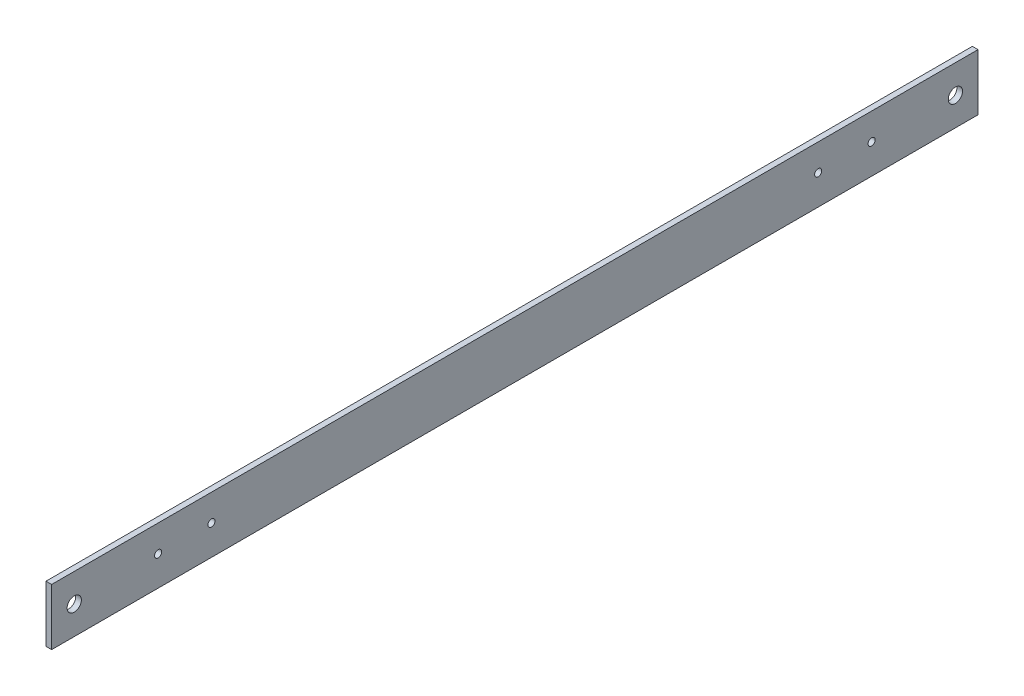
SolidWorks part; units mm, degrees
ref_plane "Front Plane" through (0, 0, 0) normal (0, 0, 1) x (1, 0, 0)
ref_plane "Top Plane" through (0, 0, 0) normal (0, 1, 0) x (1, 0, 0)
ref_plane "Right Plane" through (0, 0, 0) normal (1, 0, 0) x (0, 0, -1)
sketch "Sketch1" plane through (0, 0, 0) normal (1, 0, 0) x (0, 0, -1)
  line L1 (0, 0) -> (520.7, 0)
  line L2 (0, 0) -> (0, 31.75)
  line L3 (0, 31.75) -> (520.7, 31.75)
  line L4 (520.7, 0) -> (520.7, 31.75)
  circle A0 centre (12.7, 15.875) radius 4
  circle A1 centre (508, 15.875) radius 4
  circle A2 centre (59.825, 16.75) radius 2
  circle A3 centre (89.825, 16.75) radius 2
  circle A4 centre (430.875, 16.75) radius 2
  circle A5 centre (460.875, 16.75) radius 2
  dimension "D3" = 8
  dimension "D13" = 4
  dimension "D1" = 31.75
  dimension "D2" = 520.7
  dimension "D4" = 15.875
  dimension "D5" = 12.7
  dimension "D6" = 12.7
  dimension "D7" = 508
  dimension "D8" = 30
  dimension "D9" = 59.825
  dimension "D10" = 59.825
  dimension "D11" = 30
  dimension "D12" = 15
  dimension "D14" = 430.875
extrude "Boss-Extrude2" add sketch "Sketch1" along normal blind 3.175
equation "\"RailThickness\"= .125in'Spec"
equation "\"VSWidth\"= 1.25in'Spec"
equation "\"StepperHolePadSize\"= \"StepperHoleDiameter\""
equation "\"D1@Sketch1\"=\"TopRailHeight\""
equation "\"D2@Sketch1\"= \"FrontOrBackRailLength\""
equation "\"FrameFastenerHoleDiameter\"= 8mm"
equation "\"D3@Sketch1\"=\"FrameFastenerHoleDiameter\""
equation "\"D4@Sketch1\"=\"TopRailHeight\"/2"
equation "\"D5@Sketch1\"=\"FrameFastenerHoleOffsetFromEdge\""
equation "\"D6@Sketch1\"=\"FrameFastenerHoleOffsetFromEdge\""
equation "\"D1@Boss-Extrude2\"=\"RailThickness\""
equation "\"FrontOrBackRailLength\"= 20.5in"
equation "\"FrameFastenerHoleOffsetFromEdge\" = \"VSWidth\" / 2 - \"GapBetweenVerticalSupportsAndRails\" / 2"
equation "\"TopRailHeight\"= 1.25in"
equation "\"GapBetweenVerticalAndHorizontalRails\"= \"RailThickness\""
equation "\"GapBetweenVerticalSupportsAndRails\" = \"RailThickness\" * 2"
equation "\"AngleBracketSmallHoleDiameter\"= 4mm"
equation "\"AngleBracketSlotDistanceBetweenHoles\"= 30mm"
equation "\"AngleBracketSlotDistanceFromCorner\" = \"AngleBracketSlotDistanceFromBack\" - \"GapBetweenVerticalSupportsAndRails\" / 2'Equals 61.825"
equation "\"AngleBracketSlotDistanceFromBack\"= 65mm"
equation "\"D9@Sketch1\"= \"AngleBracketSlotDistanceFromCorner\" - 2mm'Minus 2mm to get screw hole in middle of slot"
equation "\"D8@Sketch1\"=\"AngleBracketSlotDistanceBetweenHoles\""
equation "\"D11@Sketch1\"=\"AngleBracketSlotDistanceBetweenHoles\""
equation "\"D10@Sketch1\"= \"AngleBracketSlotDistanceFromCorner\" - 2mm'Minus 2mm to get screw hole in middle of slot"
equation "\"D13@Sketch1\"=\"AngleBracketSmallHoleDiameter\""
